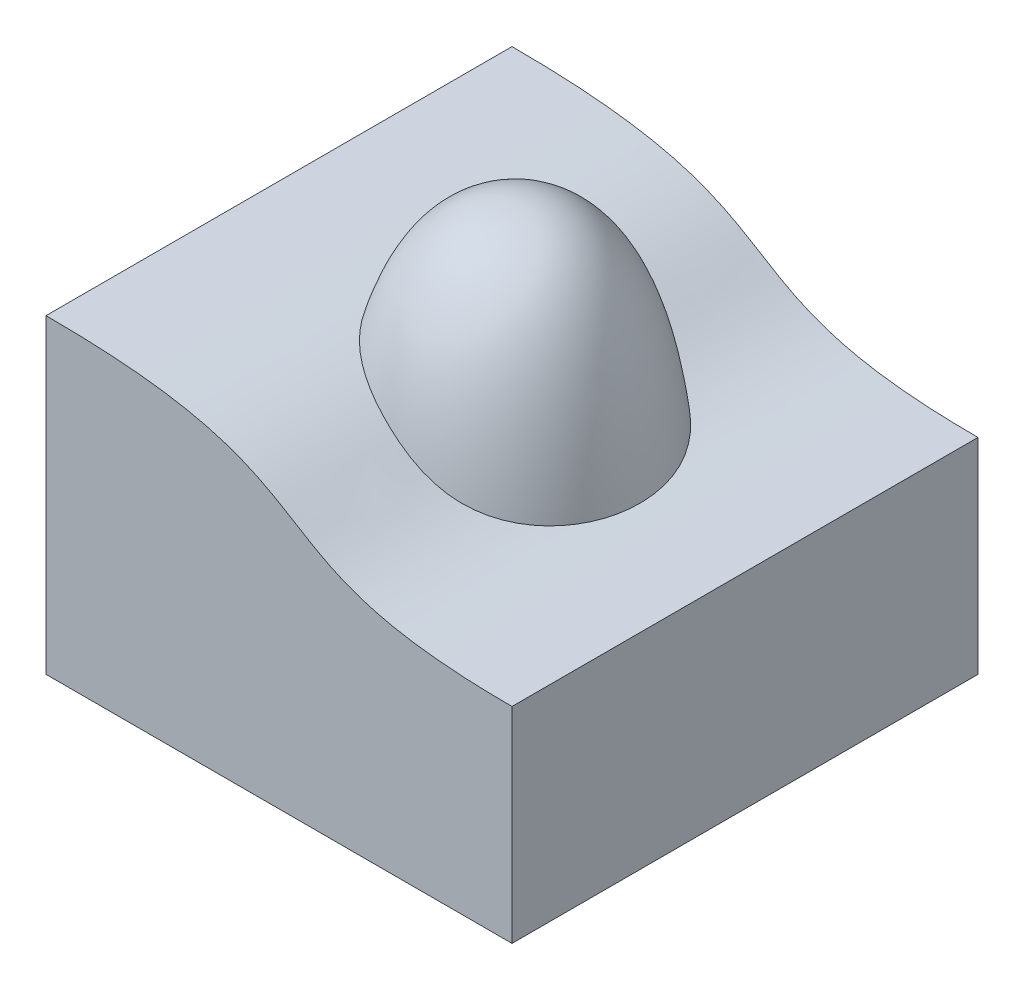
SolidWorks part; units mm, degrees
ref_plane "Front Plane" through (0, 0, 0) normal (0, 0, 1) x (1, 0, 0)
ref_plane "Top Plane" through (0, 0, 0) normal (0, 1, 0) x (1, 0, 0)
ref_plane "Right Plane" through (0, 0, 0) normal (1, 0, 0) x (0, 0, -1)
sketch "Sketch1" plane through (0, 0, 0) normal (0, 0, 1) x (1, 0, 0)
  line L1 (0, 0) -> (76.2, 0)
  line L2 (0, 0) -> (0, 50.8)
  line L3 (0, 50.8) -> (76.2, 50.8)
  line L4 (76.2, 0) -> (76.2, 50.8)
  dimension "D1" = 50.8
  dimension "D2" = 76.2
extrude "Boss-Extrude1" add sketch "Sketch1" along normal blind 38.1 and the other way blind 38.1
sketch "Sketch2" plane through (0, 0, 38.1) normal (0, 0, 1) x (1, 0, 0)
  line L0 (76.2, 0) -> (76.2, 50.8) construction
  line L1 (0, 50.8) -> (76.2, 50.8)
  line L2 (76.2, 50.8) -> (76.2, 33.5547)
  spline S0 degree 3 poles (0, 50.8) (50.6191, 50.8) (30.9636, 33.5547) (76.2, 33.5547) knots 0 0 0 0 1 1 1 1
extrude "Cut-Extrude1" cut sketch "Sketch2" against normal through all
sketch "Sketch3" plane through (0, 0, 0) normal (0, 0, 1) x (1, 0, 0)
  line L0 (38.6262, 75.6724) -> (38.6262, 16.6968) construction
  line L1 (17.7117, 28.9994) -> (38.6262, 28.9994)
  line L2 (38.6262, 28.9994) -> (38.6262, 66.9837)
  spline S0 degree 2 poles (38.6262, 66.9837) (20.1896, 66.9837) (17.7117, 28.9994) knots 0 0 0 1 1 1
revolve "Revolve1" add sketch "Sketch3" angle 360 about L0
